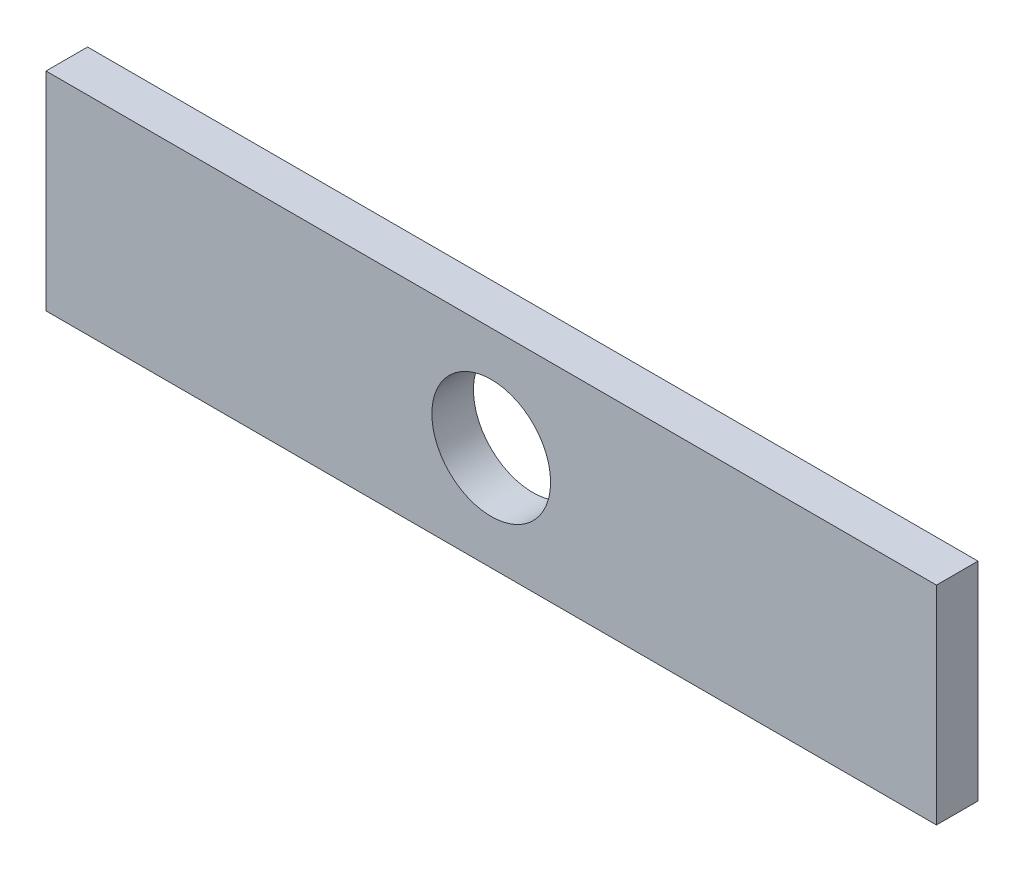
SolidWorks part; units mm, degrees
ref_plane "Front Plane" through (0, 0, 0) normal (0, 0, 1) x (1, 0, 0)
ref_plane "Top Plane" through (0, 0, 0) normal (0, 1, 0) x (1, 0, 0)
ref_plane "Right Plane" through (0, 0, 0) normal (1, 0, 0) x (0, 0, -1)
sketch "Sketch1" plane through (0, 0, 0) normal (0, 0, 1) x (1, 0, 0)
  line L1 (-75, -17.5) -> (75, -17.5)
  line L2 (-75, -17.5) -> (-75, 17.5)
  line L3 (-75, 17.5) -> (75, 17.5)
  line L4 (75, -17.5) -> (75, 17.5)
  line L5 (0, 17.5) -> (0, -17.5) construction
  line L6 (-75, 0) -> (75, 0) construction
  circle A0 centre (-60, 0) radius 5
  circle A1 centre (-35, 0) radius 5
  circle A2 centre (35, 0) radius 5
  circle A3 centre (60, 0) radius 5
  circle A4 centre (0, 0) radius 10
  point P0 (0, 0)
  dimension "D5" = 150
  dimension "D1" = 60
  dimension "D2" = 60
  dimension "D3" = 35
  dimension "D4" = 35
  dimension "D6" = 35
extrude "Boss-Extrude1" add sketch "Sketch1" along normal blind 7 contours L1 L4 L3 L2 A3 A2 A1 A0 | A1 | A0 | A2 | A3 region at (-73.4597, 0, 0) region at (-60, 0, 0) region at (-35, 0, 0) region at (35, 0, 0) region at (60, 0, 0)
extrude "Boss-Extrude2" add sketch "Sketch1<3>" against normal blind 10 contours A3 | A2 | A1 | A0 region at (-60, 0, 0) region at (-35, 0, 0) region at (35, 0, 0) region at (60, 0, 0)
sketch "Sketch1<3>" plane through (0, 0, 0) normal (0, 0, 1) x (1, 0, 0) same geometry as "Sketch1"
scale "Scale1" scale about centroid uniform scaling yes scale factor 0.2
scale "Scale2" scale about centroid uniform scaling yes scale factor 2
